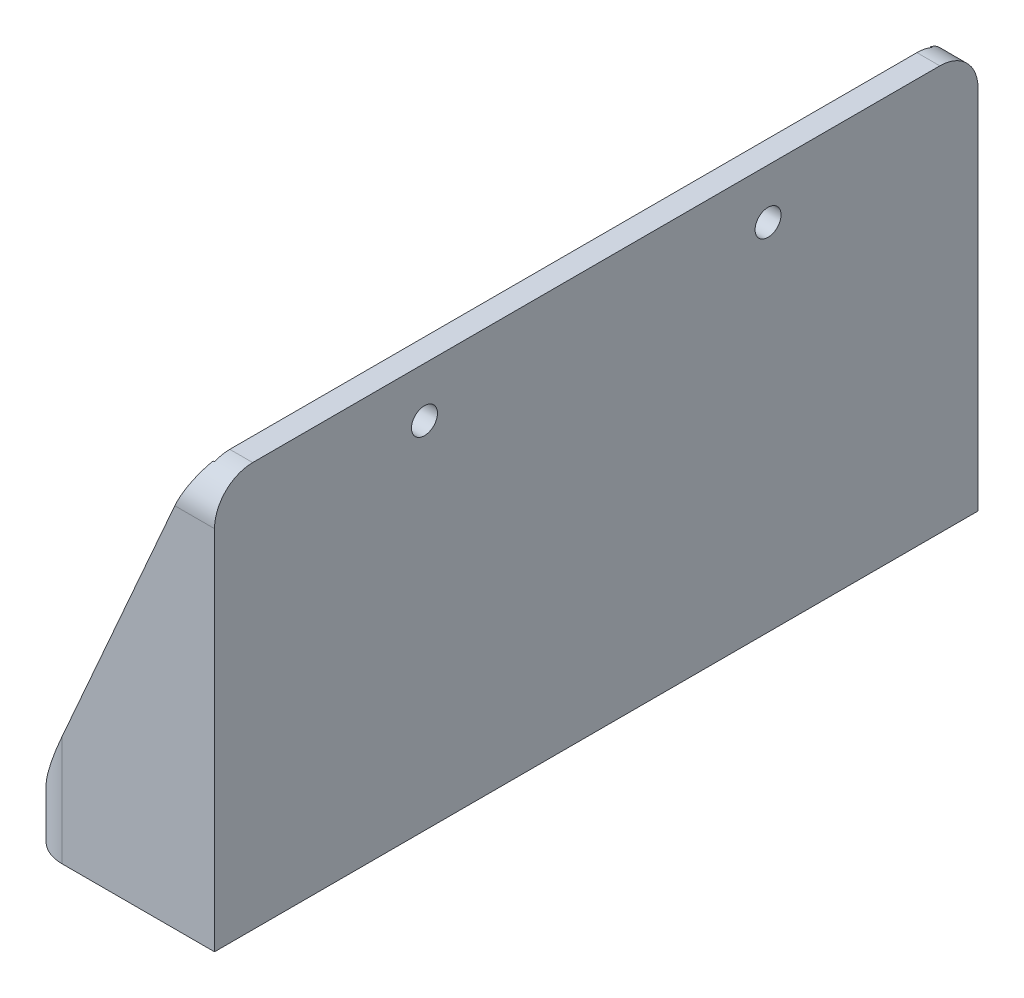
SolidWorks part; units mm, degrees
ref_plane "Front Plane" through (0, 0, 0) normal (0, 0, 1) x (1, 0, 0)
ref_plane "Top Plane" through (0, 0, 0) normal (0, 1, 0) x (1, 0, 0)
ref_plane "Right Plane" through (0, 0, 0) normal (1, 0, 0) x (0, 0, -1)
sketch "Sketch1" plane through (0, 0, 0) normal (0, 1, 0) x (1, 0, 0)
  line L1 (12.5, -50) -> (-12.5, -50)
  line L2 (12.5, -50) -> (12.5, 50)
  line L3 (12.5, 50) -> (-12.5, 50)
  line L4 (-12.5, -50) -> (-12.5, 50)
  line L5 (12.5, -50) -> (-12.5, 50) construction
  line L6 (12.5, 50) -> (-12.5, -50) construction
  point P0 (0, 0)
  dimension "D1" = 100
  dimension "D2" = 25
extrude "Boss-Extrude1" add sketch "Sketch1" along normal blind 3
sketch "Sketch2" plane through (0, 3, 0) normal (0, 1, 0) x (1, 0, 0)
  line L0 (-12.5, -50) -> (12.5, -50) construction
  line L1 (12.5, 50) -> (9.5, 50)
  line L2 (12.5, 50) -> (12.5, -50)
  line L3 (12.5, -50) -> (9.5, -50)
  line L4 (9.5, 50) -> (9.5, -50)
  dimension "D1" = 3
extrude "Boss-Extrude2" add sketch "Sketch2" along normal blind 50
sketch "Sketch3" plane through (9.5, 0, 0) normal (-1, 0, 0) x (0, 0, 1)
  line L0 (-50, 3) -> (50, 3) construction
  line L1 (0, -1.65) -> (0, 1.65) construction
  circle A0 centre (-22.5, 46.5) radius 1.7
  circle A1 centre (22.5, 46.5) radius 1.7
  dimension "D1" = 22.5
  dimension "D2" = 43.5
extrude "Cut-Extrude1" cut sketch "Sketch3" against normal blind 25
sketch "Sketch4" plane through (0, 3, 0) normal (0, 1, 0) x (1, 0, 0)
  circle A0 centre (-1.5, -1.5793) radius 2.2
  circle A1 centre (-1.5, 38.4207) radius 2.2
  circle A2 centre (-1.5, -41.5793) radius 2.2
  dimension "D1" = 40
  dimension "D2" = 40
extrude "Cut-Extrude2" cut sketch "Sketch4" against normal blind 25
fillet "Fillet1" radius 5 1 edges at (9.5, 3, 0)
sketch "Sketch5" plane through (0, 0, 50) normal (0, 0, 1) x (1, 0, 0)
  line L0 (9.5, 53) -> (-12.5, 3)
  line L1 (-12.5, 3) -> (9.5, 3)
  line L2 (9.5, 3) -> (9.5, 53.4305)
  line M4 (9.5, 53) -> (9.5, 8)
  arc M5 (9.5, 8) -> (4.5, 3) centre (4.5, 8) cw
  line M6 (4.5, 3) -> (-12.5, 3)
extrude "Boss-Extrude3" add sketch "Sketch5" against normal blind 3 contours L0 M4 M6 M5 region at (2.1054, 19.8198, 50)
mirror "Mirror1" about plane through (0, 0, 0) normal (0, 0, 1) of "Boss-Extrude3"
fillet "Fillet2" radius 5 4 edges at (-12.5, 1.5, 50) (-12.5, 1.5, -50) (11, 53, -50) (11, 53, 50)
